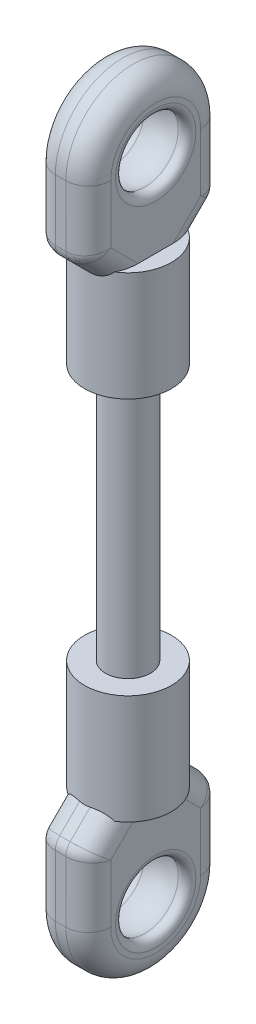
SolidWorks part; units mm, degrees
ref_plane "Front Plane" through (0, 0, 0) normal (0, 0, 1) x (1, 0, 0)
ref_plane "Top Plane" through (0, 0, 0) normal (0, 1, 0) x (1, 0, 0)
ref_plane "Right Plane" through (0, 0, 0) normal (1, 0, 0) x (0, 0, -1)
sketch "Sketch1" plane through (0, 0, 0) normal (0, 1, 0) x (1, 0, 0)
  circle A0 centre (0, 0) radius 1.5
  dimension "D1" = 3
extrude "Boss-Extrude1" add sketch "Sketch1" against normal blind 8.575
sketch "Sketch2" plane through (0, 0, 0) normal (0, 1, 0) x (1, 0, 0)
  circle A0 centre (0, 0) radius 2.9
extrude "Boss-Extrude2" add sketch "Sketch2" along normal blind 7.3
sketch "Sketch3" plane through (0, 0, 0) normal (1, 0, 0) x (0, 0, -1)
  line L0 (-4.5, 13) -> (-4.5, 8.5)
  line L1 (-4.5, 8.5) -> (0, 4)
  line L2 (0, 4) -> (4.5, 8.5)
  line L3 (4.5, 8.5) -> (4.5, 13)
  line L4 (-2.9, 0) -> (2.9, 0) construction
  arc A0 (4.5, 13) -> (-4.5, 13) centre (0, 13) ccw
  dimension "D1" = 9
  dimension "D2" = 13
  dimension "D3" = 8.5
extrude "Boss-Extrude3" add sketch "Sketch3" along normal mid plane 3.7
fillet "Fillet1" radius 1 2 edges at (0, 8.5, -4.5) (0, 8.5, 4.5)
fillet "Fillet2" radius 1.5 14 edges at (-1.85, 7.2202, -3.2202) (-1.85, 8.5315, -4.4239) (-1.85, 7.2202, 3.2202) (-1.85, 8.5315, 4.4239) (-1.85, 10.9571, 4.5) (-1.85, 17.5, 0) (1.85, 7.2202, -3.2202) (1.85, 8.5315, -4.4239) (1.85, 7.2202, 3.2202) (1.85, 8.5315, 4.4239) (1.85, 10.9571, 4.5) (1.85, 17.5, 0) (-1.85, 10.9571, -4.5) (1.85, 10.9571, -4.5)
sketch "Sketch4" plane through (0, 0, 0) normal (1, 0, 0) x (0, 0, -1)
  line L0 (0, 15.5) -> (0, 10.5) construction
  circle A0 centre (0, 13) radius 2.5
  dimension "D1" = 5
revolve "Cut-Revolve1" cut sketch "Sketch4" angle 360 about L0 region at (0, 13, -1.061)
fillet "Fillet3" radius 0.5 2 edges at (-1.85, 13, -1.6815) (1.85, 13, -1.6815)
mirror "Mirror1" about plane through (0, -8.575, 0) normal (0, 1, 0) of bodies 105
